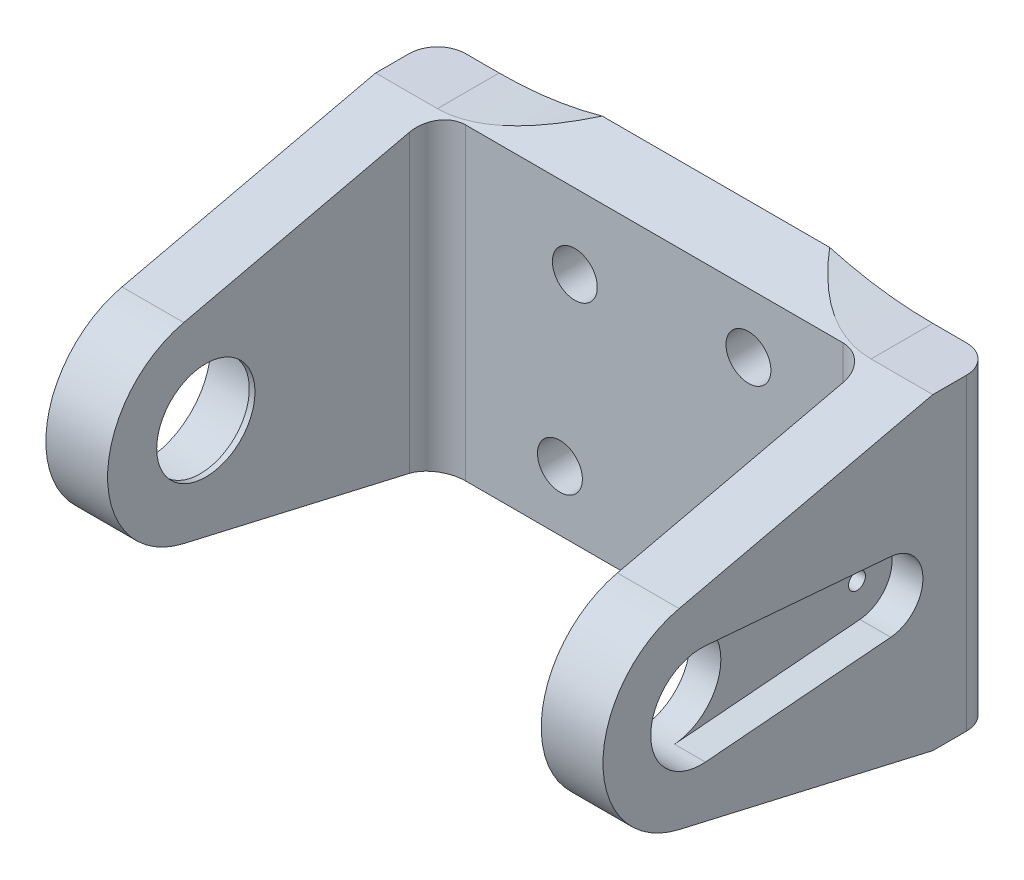
SolidWorks part; units mm, degrees
material "ABS"
ref_plane "Ön Düzlem" through (0, 0, 0) normal (0, 0, 1) x (1, 0, 0)
ref_plane "Üst Düzlem" through (0, 0, 0) normal (0, 1, 0) x (1, 0, 0)
ref_plane "Sağ Düzlem" through (0, 0, 0) normal (1, 0, 0) x (0, 0, -1)
sketch "Çizim1" plane through (0, 0, 0) normal (0, 1, 0) x (1, 0, 0)
  line L0 (-19.85, 0) -> (19.85, 0) construction
  line L1 (-19.85, -7) -> (-19.85, 20.9)
  line L2 (-19.85, -7) -> (-15.45, -7)
  line L3 (-15.45, -7) -> (-15.45, 16.5)
  line L4 (0, 0) -> (0, 16.5) construction
  line L5 (19.85, -7) -> (15.45, -7)
  line L6 (19.85, -7) -> (19.85, 20.9)
  line L7 (15.45, -7) -> (15.45, 16.5)
  line L8 (-15.45, 16.5) -> (15.45, 16.5)
  line L9 (-19.85, 20.9) -> (19.85, 20.9)
  point P4 (0, 0)
  dimension "D1" = 4.4
  dimension "D2" = 7
  dimension "D3" = 4.4
  dimension "D4" = 15.45
  dimension "D5" = 16.5
extrude "Yükseklik-Ekstrüzyon1" add sketch "Çizim1" along normal mid plane 28
sketch "Çizim2" plane through (0, 0, 0) normal (1, 0, 0) x (0, 0, -1)
  line L0 (-1.572, -6.8212) -> (20.9, -12)
  line L1 (20.9, -12) -> (20.9, 12)
  line L2 (-1.572, 6.8212) -> (20.9, 12)
  line L3 (0, 0) -> (20.9, 0) construction
  line L5 (20.9, -12) -> (20.9, -14)
  line L6 (20.9, 12) -> (20.9, 14)
  line L9 (-7, -14) -> (20.9, -14)
  line L10 (-7, 14) -> (-7, -14)
  line L11 (20.9, 14) -> (-7, 14)
  line L12 (20.9, -14) -> (20.9, 14)
  line L13 (-7, -14) -> (20.9, -14)
  line L14 (-7, 14) -> (-7, -14)
  line L15 (20.9, 14) -> (-7, 14)
  circle A0 centre (0, 0) radius 4.6 construction
  circle A1 centre (0, 0) radius 7
  point P8 (-7, 0)
  dimension "D1" = 9.2
  dimension "D3" = 24
  dimension "D5" = 0
extrude "Kes-Ekstrüzyon1" cut sketch "Çizim2" against normal through all contours A1 L14 L13 L5 L0 | A1 L2 L6 L15 L14 region at (0, -10.8054, -3.6874) region at (0, 10.8054, -3.6874)
sketch "Çizim3" plane through (0, 0, 0) normal (1, 0, 0) x (0, 0, -1)
  line L1 (20.9, -12) -> (20.9, 12) construction
  line L2 (20.9, -12) -> (20.9, -14) construction
  line L3 (-7, -14) -> (20.9, -14) construction
  line L4 (-7, 14) -> (-7, -14) construction
  line L5 (20.9, 14) -> (-7, 14) construction
  line L6 (20.9, 12) -> (20.9, 14) construction
  line L8 (-1.572, 6.8212) -> (20.9, 12)
  line L9 (20.9, -12) -> (20.9, 12)
  line L10 (20.9, -12) -> (20.9, -14)
  line L11 (-7, -14) -> (20.9, -14)
  line L12 (-7, 14) -> (-7, -14)
  line L13 (20.9, 14) -> (-7, 14)
  line L14 (20.9, 12) -> (20.9, 14)
  line L15 (-1.572, -6.8212) -> (20.9, -12)
  circle A0 centre (0, 0) radius 3.6 construction
  circle A1 centre (0, 0) radius 7
  circle A2 centre (0, 0) radius 7 construction
  dimension "D1" = 7.2
extrude "Kes-Ekstrüzyon3" cut sketch "Çizim3" along normal through all contours A1 L8 L14 L13 L12 | A1 L12 L11 L10 L15 region at (0, 10.8054, -3.6874) region at (0, -10.8054, -3.6874)
sketch "Çizim4" plane through (0, 0, -16.5) normal (0, 0, 1) x (1, 0, 0)
  line L0 (0, 0) -> (0, 14) construction
  line L1 (0, 0) -> (-14, 0) construction
  line L2 (-15.45, 10.986) -> (-19.85, 10.986)
  line L3 (-19.85, 6.8212) -> (-19.85, 12) construction
  line L4 (-19.85, 10.986) -> (-19.85, 14)
  line L5 (-19.85, 14) -> (19.85, 14)
  line L6 (-15.45, 10.986) -> (-15.45, -10.986)
  line L8 (-15.45, 10.986) -> (-15.45, -10.986)
  line L10 (15.45, 10.986) -> (19.85, 10.986)
  line L11 (19.85, 10.986) -> (19.85, 14)
  line L12 (15.45, -10.986) -> (15.45, 10.986)
  line L13 (-15.45, -10.986) -> (-19.85, -10.986)
  line L14 (-19.85, -10.986) -> (-19.85, -14)
  line L15 (-19.85, -14) -> (19.85, -14)
  line L16 (19.85, -10.986) -> (19.85, -14)
  line L17 (15.45, -10.986) -> (19.85, -10.986)
  line L22 (15.45, -10.986) -> (15.45, 10.986)
  line L23 (15.45, 10.986) -> (-15.45, 10.986)
  line L37 (15.45, 10.986) -> (-15.45, 10.986)
  line L38 (-15.45, -10.986) -> (15.45, -10.986)
  line L39 (-15.45, -10.986) -> (15.45, -10.986)
  circle A0 centre (0, 0) radius 14
  arc A1 (-15.45, 10.986) -> (-5.262, 12.9735) centre (-15.45, 38.0919) ccw
  arc A2 (-15.45, -10.986) -> (-5.262, -12.9735) centre (-15.45, -38.0919) cw
  arc A3 (15.45, -10.986) -> (5.262, -12.9735) centre (15.45, -38.0919) ccw
  arc A4 (15.45, 10.986) -> (5.262, 12.9735) centre (15.45, 38.0919) cw
  point P21 (0, 14)
  point P28 (-15.0534, 10.986)
  dimension "D2" = 28
  dimension "D1" = 0
extrude "Kes-Ekstrüzyon4" cut sketch "Çizim4" against normal through all contours A1 A0 | A4 A0 | A3 A0 | A2 A0 region at (-12.9763, 12.703, -16.5) region at (-12.9763, -12.703, -16.5) region at (12.9763, 12.703, -16.5) region at (12.9763, -12.703, -16.5)
sketch "Çizim6" plane through (19.85, 0, 0) normal (1, 0, 0) x (0, 0, -1)
  line L0 (0, 0) -> (13.3, 0) construction
  line L1 (13.5068, 2.4914) -> (0.2977, 3.5877)
  line L2 (13.5068, -2.4914) -> (0.2977, -3.5877)
  circle A0 centre (0, 0) radius 3.6
  circle A1 centre (13.3, 0) radius 2.5
  point P9 (15.8, 0)
  point P10 (-3.6, 0)
  dimension "D1" = 7.2
  dimension "D2" = 5
  dimension "D3" = 19.4
extrude "Kes-Ekstrüzyon6" cut sketch "Çizim6" against normal up to next contours A0 region at (19.85, 0, 0)
sketch "Çizim5" plane through (0, 0, -20.9) normal (0, 0, -1) x (-1, 0, 0)
  line L0 (0, 0) -> (0, -14) construction
  line L1 (5.6569, 5.6569) -> (-5.6569, -5.6569) construction
  line L2 (-6.7175, 6.7175) -> (6.7175, -6.7175) construction
  circle A0 centre (0, 0) radius 4
  circle A1 centre (0, 0) radius 14 construction
  circle A2 centre (-6.7175, 6.7175) radius 1.6
  circle A3 centre (-5.6569, -5.6569) radius 1.6
  circle A4 centre (6.7175, -6.7175) radius 1.6
  circle A5 centre (5.6569, 5.6569) radius 1.6
  point P10 (0, 0)
  point P13 (0, 0)
  dimension "D1" = 8
  dimension "D5" = 3.2
  dimension "D2" = 45
  dimension "D3" = 19
  dimension "D4" = 16
extrude "Kes-Ekstrüzyon5" cut sketch "Çizim5" against normal through all contours A3 | A2 | A5 | A4 region at (6.7175, 6.7175, -20.9) region at (5.6569, -5.6569, -20.9) region at (-6.7175, -6.7175, -20.9) region at (-5.6569, 5.6569, -20.9)
extrude "Kes-Ekstrüzyon7" cut sketch "Çizim6<3>" against normal blind 2.2 contours A0 L0 A1 L1 | L0 A0 L2 A1 | A1 region at (19.85, 1.6474, -6.9796) region at (19.85, -1.6474, -6.9796) region at (19.85, 1.7874, -11.6548)
sketch "Çizim6<3>" plane through (19.85, 0, 0) normal (1, 0, 0) x (0, 0, -1) same geometry as "Çizim6"
sketch "Çizim7" plane through (17.65, 0, 0) normal (1, 0, 0) x (0, 0, -1)
  circle A0 centre (13.3, 0) radius 0.6
  dimension "D1" = 13.3
  dimension "D2" = 1.2
extrude "Kes-Ekstrüzyon8" cut sketch "Çizim7" against normal up to next
sketch "Çizim9" plane through (-19.85, 0, 0) normal (-1, 0, 0) x (0, 0, 1)
  circle A0 centre (0, 0) radius 4.75
  circle A1 centre (0, 0) radius 3.5
  dimension "D1" = 9.5
  dimension "D2" = 7
extrude "Kes-Ekstrüzyon10" cut sketch "Çizim9" against normal up to next contours A1 region at (-19.85, 0, 0)
extrude "Kes-Ekstrüzyon11" cut sketch "Çizim9<3>" against normal blind 4
sketch "Çizim9<3>" plane through (-19.85, 0, 0) normal (-1, 0, 0) x (0, 0, 1) same geometry as "Çizim9"
fillet "Radyus1" radius 2 4 edges at (-19.85, 0, -20.9) (-15.45, 0, -16.5) (15.45, 0, -16.5) (19.85, 0, -20.9)
extrude "Kes-Ekstrüzyon12" cut sketch "Çizim5<3>" against normal blind 3 contours A0 region at (0, 0, -20.9)
sketch "Çizim5<3>" plane through (0, 0, -20.9) normal (0, 0, -1) x (-1, 0, 0) same geometry as "Çizim5"
chamfer "Pah1" distance 1.5 angle 45 1 edges at (-4, 0, -17.9)
sketch "Çizim10" plane through (0, 0, -16.5) normal (0, 0, 1) x (1, 0, 0)
  circle A0 centre (-5.6569, 5.6569) radius 2.75
  circle A1 centre (6.7175, 6.7175) radius 2.75
  circle A2 centre (5.6569, -5.6569) radius 2.75
  circle A3 centre (-6.7175, -6.7175) radius 2.75
  dimension "D1" = 5.5
extrude "Yükseklik-Ekstrüzyon2" [suppressed] add sketch "Çizim10" along normal blind 3
